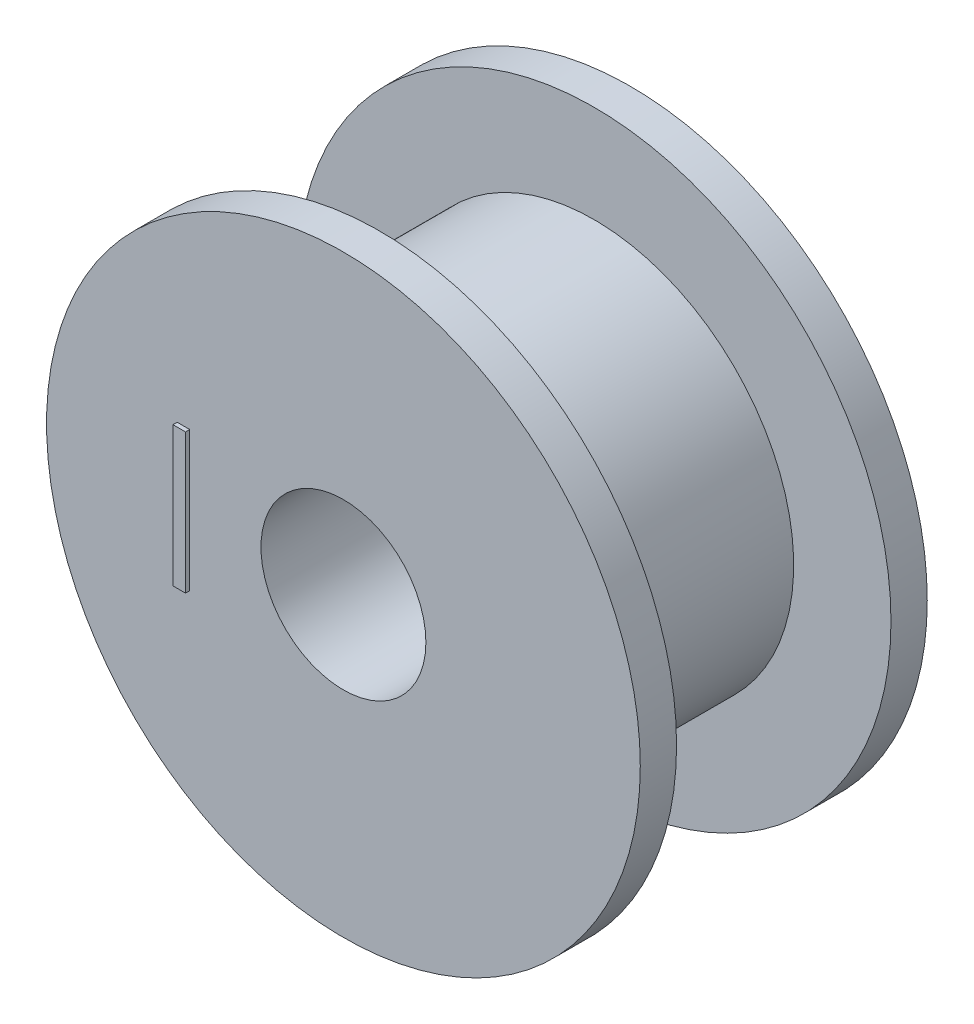
SolidWorks part; units mm, degrees
material "Chrome Stainless Steel"
ref_plane "Front Plane" through (0, 0, 0) normal (0, 0, 1) x (1, 0, 0)
ref_plane "Top Plane" through (0, 0, 0) normal (0, 1, 0) x (1, 0, 0)
ref_plane "Right Plane" through (0, 0, 0) normal (1, 0, 0) x (0, 0, -1)
sketch "Sketch1" plane through (0, 0, 0) normal (0, 0, 1) x (1, 0, 0)
  circle A0 centre (0, 0) radius 9
  dimension "D1" = 18
extrude "Boss-Extrude1" add sketch "Sketch1" along normal blind 1.1
sketch "Sketch2" plane through (0, 0, 1.1) normal (0, 0, 1) x (1, 0, 0)
  circle A0 centre (0, 0) radius 6.05
  dimension "D1" = 12.1
extrude "Boss-Extrude2" add sketch "Sketch2" along normal blind 6.5
sketch "Sketch3" plane through (0, 0, 7.6) normal (0, 0, 1) x (1, 0, 0)
  circle A0 centre (0, 0) radius 9 construction
  circle A1 centre (0, 0) radius 9
extrude "Boss-Extrude3" add sketch "Sketch3" along normal blind 1.1
sketch "Sketch4" plane through (0, 0, 8.7) normal (0, 0, 1) x (1, 0, 0)
  circle A0 centre (0, 0) radius 2.5
  dimension "D1" = 5
extrude "Cut-Extrude1" cut sketch "Sketch4" against normal up to next
sketch "Sketch5" plane through (0, 0, 8.7) normal (0, 0, 1) x (1, 0, 0)
  text T0 "I" font "Century Gothic" height in points 16
extrude "Boss-Extrude4" add sketch "Sketch5" along normal blind 0.127
ref_axis "Axis1" through (0, 0, -9.6135) along (0, 0, 1)
ref_plane "Plane1" through (0, 0, 4.35) normal (0, 0, 1) x (1, 0, 0)
